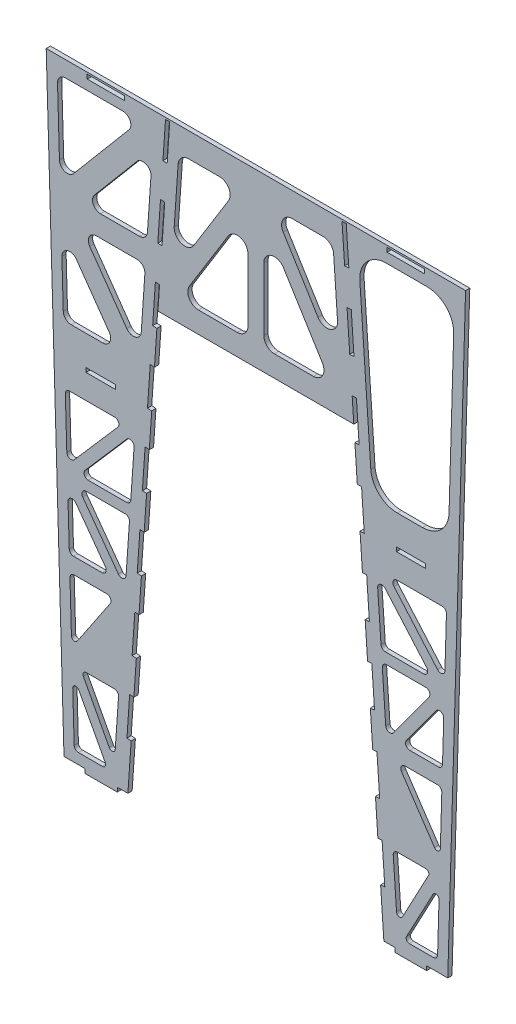
SolidWorks part; units mm, degrees
ref_plane "Front Plane" through (0, 0, 0) normal (0, 0, 1) x (1, 0, 0)
ref_plane "Top Plane" through (0, 0, 0) normal (0, 1, 0) x (1, 0, 0)
ref_plane "Right Plane" through (0, 0, 0) normal (1, 0, 0) x (0, 0, -1)
sketch "Sketch1" plane through (0, 0, 0) normal (0, 0, 1) x (1, 0, 0)
  line L0 (-288.2759, 0) -> (288.2759, 0) construction
  line L1 (-215.8925, 1465.1633) -> (215.8925, 1465.1633)
  line L2 (0, 0) -> (0, 1733.4513) construction
  line L3 (19.05, 1104.9) -> (205.6376, 1104.9)
  line L4 (202.8026, 1145.716) -> (41.4459, 1406.7433)
  line L5 (205.6376, 1104.9) -> (19.05, 1406.7433) construction
  line L6 (205.6376, 1104.9) -> (184.6725, 1406.7433)
  line L7 (183.2417, 1104.9) -> (15.2162, 1376.7154)
  line L8 (19.05, 1406.7433) -> (19.05, 1104.9)
  line L9 (184.6725, 1406.7433) -> (19.05, 1406.7433)
  line L10 (306.6278, 17.4764) -> (234.6272, 1054.1)
  line L12 (459.7218, 17.4764) -> (502.3797, 1465.1633)
  line L13 (459.4357, 7.4824) -> (519.9157, 2060.3987) construction
  line L15 (266.6925, 1465.1633) -> (368.5375, 1465.1633)
  line L16 (-237.2124, 1016.8799) -> (-230.6925, 1110.7494) construction
  line L18 (237.2124, 1016.8799) -> (230.6925, 1110.7494) construction
  line L19 (-408.9218, 7.3164) -> (-332.1008, 7.3164)
  line L20 (-502.3797, 1465.1633) -> (-215.8925, 1465.1633)
  line L22 (408.9218, 7.3164) -> (332.7218, 7.3164)
  line L24 (-408.9218, 17.4764) -> (-408.9218, 7.3164) construction
  line L30 (-408.9218, 17.4764) -> (-408.9218, 7.3164)
  line L31 (502.3797, 1465.1633) -> (368.5375, 1465.1633)
  line L32 (-332.1008, 17.4764) -> (-332.1008, 7.3164) construction
  line L33 (-332.1008, 17.4764) -> (-332.1008, 7.3164)
  line L34 (408.9218, 17.4764) -> (408.9218, 7.3164) construction
  line L35 (408.9218, 17.4764) -> (408.9218, 7.3164)
  line L40 (332.7218, 17.4764) -> (332.7218, 7.3164) construction
  line L43 (332.7218, 17.4764) -> (332.7218, 7.3164)
  line L44 (459.7218, 17.4764) -> (408.9218, 17.4764) construction
  line L45 (459.7218, 17.4764) -> (408.9218, 17.4764)
  line L49 (-408.9218, 17.4764) -> (-459.7218, 17.4764)
  line L52 (-332.1008, 17.4764) -> (-306.6278, 17.4764)
  line L53 (332.7218, 17.4764) -> (306.6278, 17.4764)
  line L55 (-459.7218, 17.4764) -> (-502.3797, 1465.1633)
  line L56 (-459.4357, 7.4824) -> (-519.9157, 2060.3987) construction
  line L81 (215.8925, 1465.1633) -> (266.6925, 1465.1633)
  line L90 (234.6272, 1054.1) -> (-234.6272, 1054.1)
  line L100 (-234.6272, 1054.1) -> (-306.6278, 17.4764)
  line L124 (-184.6725, 1406.7433) -> (-19.05, 1406.7433)
  line L125 (-19.05, 1406.7433) -> (-19.05, 1104.9)
  line L126 (-183.2417, 1104.9) -> (-15.2162, 1376.7154)
  line L127 (-205.6376, 1104.9) -> (-19.05, 1406.7433) construction
  line L128 (-202.8026, 1145.716) -> (-41.4459, 1406.7433)
  line L129 (-205.6376, 1104.9) -> (-184.6725, 1406.7433)
  line L130 (-19.05, 1104.9) -> (-205.6376, 1104.9)
  point P0 (0, 0)
  point P3 (0, 0)
  point P106 (0, 0)
  point P118 (0, 1054.1)
  dimension "D6" = 25.4
  dimension "D7" = 50.8
  dimension "D8" = 58.42
  dimension "D9" = 19.05
  dimension "D19" = 288.2759
  dimension "D22" = 19.05
  dimension "D23" = 19.05
  dimension "D24" = 1054.1
  dimension "D49" = 50.8
extrude "Boss-Extrude1" add sketch "Sketch1" along normal blind 10.16 contours L20 | L100 L90 L125 L130 L129 L124 | L100 | L130 L126 L125 L124 L128 L129 | L81 | L4 L9 L8 L7 L3 L6 | L15 region at (0, 1447.4578, 0) region at (111.9691, 1256.3298, 0) region at (-111.9691, 1256.3298, 0)
fillet "Fillet1" [suppressed] radius 19.05
sketch "Sketch2" plane through (0, 0, 0) normal (0, 0, 1) x (1, 0, 0)
  line L18 (-222.6942, 1372.2749) -> (-212.5765, 1371.5721) construction
  line L56 (-216.5353, 1460.9479) -> (-222.6942, 1372.2749) construction
  line L57 (-212.5765, 1371.5721) -> (-206.3688, 1460.9479) construction
  line L58 (-206.3688, 1460.9479) -> (-216.5353, 1460.9479) construction
  line L59 (-222.6942, 1372.2749) -> (-212.5765, 1371.5721)
  line L61 (-216.5353, 1460.9479) -> (-222.6942, 1372.2749)
  line L63 (-212.5765, 1371.5721) -> (-206.3688, 1460.9479)
  line L176 (-206.3688, 1460.9479) -> (-216.5353, 1460.9479)
  line L181 (-224.8945, 1194.226) -> (-235.0121, 1194.9287) construction
  line L194 (-224.8945, 1194.226) -> (-218.3727, 1288.1221) construction
  line L199 (-218.3727, 1288.1221) -> (-228.4904, 1288.8248) construction
  line L208 (-228.4904, 1288.8248) -> (-235.0121, 1194.9287) construction
  line L213 (-224.8945, 1194.226) -> (-235.0121, 1194.9287)
  line L330 (-224.8945, 1194.226) -> (-218.3727, 1288.1221)
  line L331 (-218.3727, 1288.1221) -> (-228.4904, 1288.8248)
  line L332 (-228.4904, 1288.8248) -> (-235.0121, 1194.9287)
  line L333 (224.8945, 1194.226) -> (235.0121, 1194.9287) construction
  line L334 (235.0121, 1194.9287) -> (228.4904, 1288.8248) construction
  line L335 (218.3727, 1288.1221) -> (224.8945, 1194.226) construction
  line L336 (228.4904, 1288.8248) -> (218.3727, 1288.1221) construction
  line L337 (212.5765, 1371.5721) -> (222.6942, 1372.2749) construction
  line L338 (206.3688, 1460.9479) -> (212.5765, 1371.5721) construction
  line L339 (216.5353, 1460.9479) -> (206.3688, 1460.9479) construction
  line L340 (222.6942, 1372.2749) -> (216.5353, 1460.9479) construction
  line L341 (224.8945, 1194.226) -> (235.0121, 1194.9287)
  line L342 (235.0121, 1194.9287) -> (228.4904, 1288.8248)
  line L343 (218.3727, 1288.1221) -> (224.8945, 1194.226)
  line L344 (228.4904, 1288.8248) -> (218.3727, 1288.1221)
  line L345 (212.5765, 1371.5721) -> (222.6942, 1372.2749)
  line L346 (206.3688, 1460.9479) -> (212.5765, 1371.5721)
  line L347 (216.5353, 1460.9479) -> (206.3688, 1460.9479)
  line L348 (222.6942, 1372.2749) -> (216.5353, 1460.9479)
  line L349 (-240.8102, 1111.4521) -> (-247.33, 1017.5826) construction
  line L350 (-247.33, 1017.5826) -> (-237.2124, 1016.8799) construction
  line L351 (-230.6925, 1110.7494) -> (-240.8102, 1111.4521) construction
  line L353 (-240.8102, 1111.4521) -> (-247.33, 1017.5826)
  line L354 (-247.33, 1017.5826) -> (-237.2124, 1016.8799)
  line L355 (-230.6925, 1110.7494) -> (-240.8102, 1111.4521)
  line L357 (237.2124, 1016.8799) -> (247.33, 1017.5826) construction
  line L358 (247.33, 1017.5826) -> (240.8102, 1111.4521) construction
  line L360 (240.8102, 1111.4521) -> (230.6925, 1110.7494) construction
  line L361 (237.2124, 1016.8799) -> (247.33, 1017.5826)
  line L362 (247.33, 1017.5826) -> (240.8102, 1111.4521)
  line L364 (240.8102, 1111.4521) -> (230.6925, 1110.7494)
  line L365 (-306.6278, 17.4764) -> (-234.6272, 1054.1)
  line L366 (-234.6272, 1054.1) -> (234.6272, 1054.1)
  line L367 (234.6272, 1054.1) -> (306.6278, 17.4764)
  line L372 (408.9218, 17.4764) -> (459.7218, 17.4764)
  line L373 (459.7218, 17.4764) -> (502.3797, 1465.1633)
  line L374 (502.3797, 1465.1633) -> (-502.3797, 1465.1633)
  line L375 (-502.3797, 1465.1633) -> (-459.7218, 17.4764)
  line L376 (-459.7218, 17.4764) -> (-408.9218, 17.4764)
  line L377 (-408.9218, 17.4764) -> (-408.9218, 7.3164)
  line L378 (-408.9218, 7.3164) -> (-332.1008, 7.3164)
  line L379 (-332.1008, 7.3164) -> (-332.1008, 17.4764)
  line L380 (-332.1008, 17.4764) -> (-306.6278, 17.4764)
  line L381 (-298.8019, 130.1492) -> (-292.2913, 223.886)
  line L405 (-243.0122, 933.3767) -> (-253.1299, 934.0795) construction
  line L406 (-253.1299, 934.0795) -> (-259.648, 840.2365) construction
  line L407 (-249.5303, 839.5337) -> (-259.648, 840.2365) construction
  line L408 (-243.0122, 933.3767) -> (-253.1299, 934.0795)
  line L417 (-253.1299, 934.0795) -> (-259.648, 840.2365)
  line L418 (-249.5303, 839.5337) -> (-259.648, 840.2365)
  line L419 (243.0122, 933.3767) -> (253.1299, 934.0795) construction
  line L420 (253.1299, 934.0795) -> (259.648, 840.2365) construction
  line L421 (249.5303, 839.5337) -> (259.648, 840.2365) construction
  line L422 (243.0122, 933.3767) -> (253.1299, 934.0795)
  line L423 (253.1299, 934.0795) -> (259.648, 840.2365)
  line L424 (249.5303, 839.5337) -> (259.648, 840.2365)
  line L425 (-267.6517, 578.6314) -> (-277.7694, 579.3341) construction
  line L426 (-255.332, 756.0041) -> (-265.4497, 756.7068) construction
  line L427 (-265.4497, 756.7068) -> (-271.9659, 662.8903) construction
  line L428 (-261.8482, 662.1876) -> (-271.9659, 662.8903) construction
  line L429 (-277.7694, 579.3341) -> (-284.2838, 485.5442) construction
  line L430 (-274.1661, 484.8415) -> (-284.2838, 485.5442) construction
  line L431 (-274.1661, 484.8415) -> (-284.2838, 485.5442)
  line L432 (-277.7694, 579.3341) -> (-284.2838, 485.5442)
  line L433 (-267.6517, 578.6314) -> (-277.7694, 579.3341)
  line L434 (-261.8482, 662.1876) -> (-271.9659, 662.8903)
  line L435 (-265.4497, 756.7068) -> (-271.9659, 662.8903)
  line L436 (-255.332, 756.0041) -> (-265.4497, 756.7068)
  line L437 (261.8482, 662.1876) -> (271.9659, 662.8903) construction
  line L438 (255.332, 756.0041) -> (265.4497, 756.7068) construction
  line L439 (265.4497, 756.7068) -> (271.9659, 662.8903) construction
  line L440 (261.8482, 662.1876) -> (271.9659, 662.8903)
  line L449 (255.332, 756.0041) -> (265.4497, 756.7068)
  line L450 (265.4497, 756.7068) -> (271.9659, 662.8903)
  line L451 (274.1661, 484.8415) -> (284.2838, 485.5442) construction
  line L452 (277.7694, 579.3341) -> (284.2838, 485.5442) construction
  line L453 (267.6517, 578.6314) -> (277.7694, 579.3341) construction
  line L454 (274.1661, 484.8415) -> (284.2838, 485.5442)
  line L455 (277.7694, 579.3341) -> (284.2838, 485.5442)
  line L456 (267.6517, 578.6314) -> (277.7694, 579.3341)
  line L457 (-298.8019, 130.1492) -> (-308.9196, 130.8519) construction
  line L458 (-302.4089, 224.5888) -> (-308.9196, 130.8519) construction
  line L459 (-292.2913, 223.886) -> (-302.4089, 224.5888) construction
  line L460 (-286.484, 307.4953) -> (-296.6017, 308.1981) construction
  line L461 (-290.0892, 401.9615) -> (-296.6017, 308.1981) construction
  line L462 (-279.9715, 401.2587) -> (-290.0892, 401.9615) construction
  line L463 (-298.8019, 130.1492) -> (-308.9196, 130.8519)
  line L464 (-302.4089, 224.5888) -> (-308.9196, 130.8519)
  line L465 (-292.2913, 223.886) -> (-302.4089, 224.5888)
  line L466 (-286.484, 307.4953) -> (-296.6017, 308.1981)
  line L467 (-290.0892, 401.9615) -> (-296.6017, 308.1981)
  line L468 (-279.9715, 401.2587) -> (-290.0892, 401.9615)
  line L469 (286.484, 307.4953) -> (296.6017, 308.1981) construction
  line L470 (279.9715, 401.2587) -> (290.0892, 401.9615) construction
  line L471 (290.0892, 401.9615) -> (296.6017, 308.1981) construction
  line L472 (286.484, 307.4953) -> (296.6017, 308.1981)
  line L473 (279.9715, 401.2587) -> (290.0892, 401.9615)
  line L474 (290.0892, 401.9615) -> (296.6017, 308.1981)
  line L475 (298.8019, 130.1492) -> (308.9196, 130.8519) construction
  line L476 (302.4089, 224.5888) -> (308.9196, 130.8519) construction
  line L477 (292.2913, 223.886) -> (302.4089, 224.5888) construction
  line L478 (298.8019, 130.1492) -> (308.9196, 130.8519)
  line L479 (302.4089, 224.5888) -> (308.9196, 130.8519)
  line L480 (292.2913, 223.886) -> (302.4089, 224.5888)
  line L481 (-230.6925, 1110.7494) -> (-237.2124, 1016.8799)
  line L482 (243.0122, 933.3767) -> (249.5303, 839.5337)
  line L483 (255.332, 756.0041) -> (261.8482, 662.1876)
  line L484 (-249.5303, 839.5337) -> (-243.0122, 933.3767)
  line L485 (-261.8482, 662.1876) -> (-255.332, 756.0041)
  line L486 (267.6517, 578.6314) -> (274.1661, 484.8415)
  line L487 (-286.484, 307.4953) -> (-279.9715, 401.2587)
  line L488 (-274.1661, 484.8415) -> (-267.6517, 578.6314)
  line L489 (279.9715, 401.2587) -> (286.484, 307.4953)
  line L490 (292.2913, 223.886) -> (298.8019, 130.1492)
  line L492 (230.6925, 1110.7494) -> (237.2124, 1016.8799)
  line L499 (306.6278, 17.4764) -> (332.7218, 17.4764)
  line L500 (332.7218, 17.4764) -> (332.7218, 7.3164)
  line L501 (332.7218, 7.3164) -> (408.9218, 7.3164)
  line L502 (408.9218, 7.3164) -> (408.9218, 17.4764)
  dimension "D1" = 0
extrude "Cut-Extrude5" cut sketch "Sketch2" along normal blind 12.7
sketch "Sketch4" plane through (0, 0, 10.16) normal (0, 0, 1) x (1, 0, 0)
  line L0 (404.2136, 1450.7879) -> (404.2136, 1460.9479) construction
  line L1 (314.2136, 1450.7879) -> (404.2136, 1450.7879) construction
  line L2 (314.2136, 1450.7879) -> (314.2136, 1460.9479) construction
  line L3 (404.2136, 1460.9479) -> (314.2136, 1460.9479) construction
  line L4 (404.2136, 1450.7879) -> (404.2136, 1460.9479)
  line L5 (314.2136, 1450.7879) -> (404.2136, 1450.7879)
  line L6 (314.2136, 1450.7879) -> (314.2136, 1460.9479)
  line L7 (404.2136, 1460.9479) -> (314.2136, 1460.9479)
  line L8 (336.7821, 840.6279) -> (336.7821, 850.7879) construction
  line L9 (336.7821, 840.6279) -> (406.7821, 840.6279) construction
  line L10 (406.7821, 840.6279) -> (406.7821, 850.7879) construction
  line L11 (406.7821, 850.7879) -> (336.7821, 850.7879) construction
  line L12 (336.7821, 840.6279) -> (336.7821, 850.7879)
  line L13 (336.7821, 840.6279) -> (406.7821, 840.6279)
  line L14 (406.7821, 840.6279) -> (406.7821, 850.7879)
  line L15 (406.7821, 850.7879) -> (336.7821, 850.7879)
extrude "Cut-Extrude6" cut sketch "Sketch4" against normal through all both
ref_plane "Plane1" through (0, 0, 0) normal (1, 0, 0) x (0, 0, -1)
mirror "Mirror1" about plane through (0, 0, 0) normal (1, 0, 0) of "Cut-Extrude6"
sketch "Sketch5" plane through (0, 0, 10.16) normal (0, 0, 1) x (1, 0, 0)
  line L0 (435.0592, 42.8764) -> (475.846, 1427.0633)
  line L1 (475.846, 1427.0633) -> (244.35, 1427.0633)
  line L2 (244.35, 1427.0633) -> (340.4913, 42.8764)
  line L3 (340.4913, 42.8764) -> (435.0592, 42.8764)
  line L4 (281.2007, 896.5079) -> (460.2126, 896.5079)
  line L5 (457.2188, 794.9079) -> (288.2575, 794.9079)
  line L6 (336.7821, 840.6279) -> (406.7821, 840.6279) construction
  line L7 (475.846, 1427.0633) -> (460.2126, 896.5079)
  line L8 (468.0293, 1161.7856) -> (281.2007, 896.5079) construction
  line L9 (244.35, 1427.0633) -> (468.0293, 1161.7856) construction
  line L10 (244.35, 1427.0633) -> (281.2007, 896.5079)
  line L11 (281.2007, 896.5079) -> (244.35, 1427.0633)
  line L12 (262.7753, 1161.7856) -> (468.0293, 1161.7856) construction
  line L13 (435.0592, 42.8764) -> (457.2188, 794.9079)
  line L14 (446.139, 418.8922) -> (457.2188, 794.9079)
  line L15 (451.6789, 606.9001) -> (288.2575, 794.9079) construction
  line L16 (451.6789, 606.9001) -> (314.3744, 418.8922) construction
  line L17 (446.139, 418.8922) -> (435.0592, 42.8764)
  line L18 (440.5991, 230.8843) -> (314.3744, 418.8922) construction
  line L19 (440.5991, 230.8843) -> (340.4913, 42.8764) construction
  line L20 (451.6789, 606.9001) -> (301.316, 606.9001) construction
  line L21 (314.3744, 418.8922) -> (446.139, 418.8922) construction
  line L22 (440.5991, 230.8843) -> (327.4329, 230.8843) construction
  line L23 (354.8795, 42.8764) -> (439.7562, 202.2796)
  line L24 (338.831, 66.78) -> (419.4486, 218.1843)
  line L25 (328.315, 218.1843) -> (419.4486, 218.1843)
  line L26 (326.5508, 243.5843) -> (416.7758, 243.5843)
  line L27 (416.7758, 243.5843) -> (316.1395, 393.479)
  line L28 (441.2422, 252.7104) -> (338.1977, 406.1922)
  line L29 (338.1977, 406.1922) -> (445.7648, 406.1922)
  line L30 (446.8874, 444.2922) -> (348.6506, 444.2922)
  line L31 (348.6506, 444.2922) -> (451.0177, 584.4611)
  line L32 (313.0087, 438.5556) -> (426.6777, 594.2001)
  line L33 (426.6777, 594.2001) -> (302.1981, 594.2001)
  line L34 (300.4339, 619.6001) -> (423.8126, 619.6001)
  line L35 (423.8126, 619.6001) -> (289.7189, 773.8679)
  line L36 (452.2306, 625.6241) -> (316.1239, 782.2079)
  line L37 (316.1239, 782.2079) -> (456.8446, 782.2079)
  line L38 (277.5742, 1427.0633) -> (469.1512, 1199.8582)
  line L39 (247.3325, 1384.1232) -> (413.3881, 1187.1856)
  line L40 (413.3881, 1187.1856) -> (261.0111, 1187.1856)
  line L41 (264.5396, 1136.3856) -> (419.0736, 1136.3856)
  line L42 (419.0736, 1136.3856) -> (278.4119, 936.6601)
  line L43 (466.6727, 1115.7474) -> (330.1564, 921.9079)
  line L44 (330.1564, 921.9079) -> (460.961, 921.9079)
  line L64 (-234.6272, 1054.1) -> (234.6272, 1054.1)
  line L65 (234.6272, 1054.1) -> (230.6925, 1110.7494)
  line L66 (230.6925, 1110.7494) -> (240.8102, 1111.4521)
  line L67 (240.8102, 1111.4521) -> (247.33, 1017.5826)
  line L68 (247.33, 1017.5826) -> (237.2124, 1016.8799)
  line L69 (237.2124, 1016.8799) -> (243.0122, 933.3767)
  line L70 (243.0122, 933.3767) -> (253.1299, 934.0795)
  line L71 (253.1299, 934.0795) -> (259.648, 840.2365)
  line L72 (259.648, 840.2365) -> (249.5303, 839.5337)
  line L73 (249.5303, 839.5337) -> (255.332, 756.0041)
  line L74 (255.332, 756.0041) -> (265.4497, 756.7068)
  line L75 (265.4497, 756.7068) -> (271.9659, 662.8903)
  line L76 (271.9659, 662.8903) -> (261.8482, 662.1876)
  line L77 (261.8482, 662.1876) -> (267.6517, 578.6314)
  line L78 (267.6517, 578.6314) -> (277.7694, 579.3341)
  line L79 (277.7694, 579.3341) -> (284.2838, 485.5442)
  line L80 (284.2838, 485.5442) -> (274.1661, 484.8415)
  line L81 (274.1661, 484.8415) -> (279.9715, 401.2587)
  line L82 (279.9715, 401.2587) -> (290.0892, 401.9615)
  line L83 (290.0892, 401.9615) -> (296.6017, 308.1981)
  line L84 (296.6017, 308.1981) -> (286.484, 307.4953)
  line L85 (286.484, 307.4953) -> (292.2913, 223.886)
  line L86 (292.2913, 223.886) -> (302.4089, 224.5888)
  line L87 (302.4089, 224.5888) -> (308.9196, 130.8519)
  line L88 (308.9196, 130.8519) -> (298.8019, 130.1492)
  line L89 (298.8019, 130.1492) -> (306.6278, 17.4764)
  line L90 (306.6278, 17.4764) -> (332.7218, 17.4764)
  line L91 (332.7218, 17.4764) -> (332.7218, 7.3164)
  line L92 (332.7218, 7.3164) -> (408.9218, 7.3164)
  line L93 (408.9218, 7.3164) -> (408.9218, 17.4764)
  line L94 (408.9218, 17.4764) -> (459.7218, 17.4764)
  line L95 (459.7218, 17.4764) -> (502.3797, 1465.1633)
  line L96 (502.3797, 1465.1633) -> (-502.3797, 1465.1633)
  line L97 (-502.3797, 1465.1633) -> (-459.7218, 17.4764)
  line L98 (-459.7218, 17.4764) -> (-408.9218, 17.4764)
  line L99 (-408.9218, 17.4764) -> (-408.9218, 7.3164)
  line L100 (-408.9218, 7.3164) -> (-332.1008, 7.3164)
  line L101 (-332.1008, 7.3164) -> (-332.1008, 17.4764)
  line L102 (-332.1008, 17.4764) -> (-306.6278, 17.4764)
  line L103 (-306.6278, 17.4764) -> (-298.8019, 130.1492)
  line L104 (-298.8019, 130.1492) -> (-308.9196, 130.8519)
  line L105 (-308.9196, 130.8519) -> (-302.4089, 224.5888)
  line L106 (-302.4089, 224.5888) -> (-292.2913, 223.886)
  line L107 (-292.2913, 223.886) -> (-286.484, 307.4953)
  line L108 (-286.484, 307.4953) -> (-296.6017, 308.1981)
  line L109 (-296.6017, 308.1981) -> (-290.0892, 401.9615)
  line L110 (-290.0892, 401.9615) -> (-279.9715, 401.2587)
  line L111 (-279.9715, 401.2587) -> (-274.1661, 484.8415)
  line L112 (-274.1661, 484.8415) -> (-284.2838, 485.5442)
  line L113 (-284.2838, 485.5442) -> (-277.7694, 579.3341)
  line L114 (-277.7694, 579.3341) -> (-267.6517, 578.6314)
  line L115 (-267.6517, 578.6314) -> (-261.8482, 662.1876)
  line L116 (-261.8482, 662.1876) -> (-271.9659, 662.8903)
  line L117 (-271.9659, 662.8903) -> (-265.4497, 756.7068)
  line L118 (-265.4497, 756.7068) -> (-255.332, 756.0041)
  line L119 (-255.332, 756.0041) -> (-249.5303, 839.5337)
  line L120 (-249.5303, 839.5337) -> (-259.648, 840.2365)
  line L121 (-259.648, 840.2365) -> (-253.1299, 934.0795)
  line L122 (-253.1299, 934.0795) -> (-243.0122, 933.3767)
  line L123 (-243.0122, 933.3767) -> (-237.2124, 1016.8799)
  line L124 (-237.2124, 1016.8799) -> (-247.33, 1017.5826)
  line L125 (-247.33, 1017.5826) -> (-240.8102, 1111.4521)
  line L126 (-240.8102, 1111.4521) -> (-230.6925, 1110.7494)
  line L127 (-230.6925, 1110.7494) -> (-234.6272, 1054.1)
  line L128 (-234.6272, 1054.1) -> (234.6272, 1054.1)
  line L129 (234.6272, 1054.1) -> (230.6925, 1110.7494)
  line L130 (230.6925, 1110.7494) -> (240.8102, 1111.4521)
  line L131 (240.8102, 1111.4521) -> (247.33, 1017.5826)
  line L132 (247.33, 1017.5826) -> (237.2124, 1016.8799)
  line L133 (237.2124, 1016.8799) -> (243.0122, 933.3767)
  line L134 (243.0122, 933.3767) -> (253.1299, 934.0795)
  line L135 (253.1299, 934.0795) -> (259.648, 840.2365)
  line L136 (259.648, 840.2365) -> (249.5303, 839.5337)
  line L137 (249.5303, 839.5337) -> (255.332, 756.0041)
  line L138 (255.332, 756.0041) -> (265.4497, 756.7068)
  line L139 (265.4497, 756.7068) -> (271.9659, 662.8903)
  line L140 (271.9659, 662.8903) -> (261.8482, 662.1876)
  line L141 (261.8482, 662.1876) -> (267.6517, 578.6314)
  line L142 (267.6517, 578.6314) -> (277.7694, 579.3341)
  line L143 (277.7694, 579.3341) -> (284.2838, 485.5442)
  line L144 (284.2838, 485.5442) -> (274.1661, 484.8415)
  line L145 (274.1661, 484.8415) -> (279.9715, 401.2587)
  line L146 (279.9715, 401.2587) -> (290.0892, 401.9615)
  line L147 (290.0892, 401.9615) -> (296.6017, 308.1981)
  line L148 (296.6017, 308.1981) -> (286.484, 307.4953)
  line L149 (286.484, 307.4953) -> (292.2913, 223.886)
  line L150 (292.2913, 223.886) -> (302.4089, 224.5888)
  line L151 (302.4089, 224.5888) -> (308.9196, 130.8519)
  line L152 (308.9196, 130.8519) -> (298.8019, 130.1492)
  line L153 (298.8019, 130.1492) -> (306.6278, 17.4764)
  line L154 (306.6278, 17.4764) -> (332.7218, 17.4764)
  line L155 (332.7218, 17.4764) -> (332.7218, 7.3164)
  line L156 (332.7218, 7.3164) -> (408.9218, 7.3164)
  line L157 (408.9218, 7.3164) -> (408.9218, 17.4764)
  line L158 (408.9218, 17.4764) -> (459.7218, 17.4764)
  line L159 (459.7218, 17.4764) -> (502.3797, 1465.1633)
  line L160 (502.3797, 1465.1633) -> (-502.3797, 1465.1633)
  line L161 (-502.3797, 1465.1633) -> (-459.7218, 17.4764)
  line L162 (-459.7218, 17.4764) -> (-408.9218, 17.4764)
  line L163 (-408.9218, 17.4764) -> (-408.9218, 7.3164)
  line L164 (-408.9218, 7.3164) -> (-332.1008, 7.3164)
  line L165 (-332.1008, 7.3164) -> (-332.1008, 17.4764)
  line L166 (-332.1008, 17.4764) -> (-306.6278, 17.4764)
  line L167 (-306.6278, 17.4764) -> (-298.8019, 130.1492)
  line L168 (-298.8019, 130.1492) -> (-308.9196, 130.8519)
  line L169 (-308.9196, 130.8519) -> (-302.4089, 224.5888)
  line L170 (-302.4089, 224.5888) -> (-292.2913, 223.886)
  line L171 (-292.2913, 223.886) -> (-286.484, 307.4953)
  line L172 (-286.484, 307.4953) -> (-296.6017, 308.1981)
  line L173 (-296.6017, 308.1981) -> (-290.0892, 401.9615)
  line L174 (-290.0892, 401.9615) -> (-279.9715, 401.2587)
  line L175 (-279.9715, 401.2587) -> (-274.1661, 484.8415)
  line L176 (-274.1661, 484.8415) -> (-284.2838, 485.5442)
  line L177 (-284.2838, 485.5442) -> (-277.7694, 579.3341)
  line L178 (-277.7694, 579.3341) -> (-267.6517, 578.6314)
  line L179 (-267.6517, 578.6314) -> (-261.8482, 662.1876)
  line L180 (-261.8482, 662.1876) -> (-271.9659, 662.8903)
  line L181 (-271.9659, 662.8903) -> (-265.4497, 756.7068)
  line L182 (-265.4497, 756.7068) -> (-255.332, 756.0041)
  line L183 (-255.332, 756.0041) -> (-249.5303, 839.5337)
  line L184 (-249.5303, 839.5337) -> (-259.648, 840.2365)
  line L185 (-259.648, 840.2365) -> (-253.1299, 934.0795)
  line L186 (-253.1299, 934.0795) -> (-243.0122, 933.3767)
  line L187 (-243.0122, 933.3767) -> (-237.2124, 1016.8799)
  line L188 (-237.2124, 1016.8799) -> (-247.33, 1017.5826)
  line L189 (-247.33, 1017.5826) -> (-240.8102, 1111.4521)
  line L190 (-240.8102, 1111.4521) -> (-230.6925, 1110.7494)
  line L191 (-230.6925, 1110.7494) -> (-234.6272, 1054.1)
  dimension "D2" = 38.1
  dimension "D3" = 25.4
  dimension "D4" = 25.4
  dimension "D5" = 25.4
  dimension "D6" = 101.6
  dimension "D7" = 45.72
  dimension "D8" = 12.7
  dimension "D9" = 12.7
  dimension "D10" = 12.7
  dimension "D11" = 12.7
  dimension "D12" = 12.7
  dimension "D13" = 12.7
  dimension "D14" = 12.7
  dimension "D15" = 25.4
  dimension "D16" = 12.7
  dimension "D17" = 12.7
  dimension "D18" = 12.7
  dimension "D19" = 12.7
  dimension "D20" = 12.7
  dimension "D21" = 12.7
  dimension "D22" = 12.7
  dimension "D23" = 25.4
  dimension "D24" = 25.4
  dimension "D25" = 25.4
  dimension "D26" = 25.4
  dimension "D27" = 25.4
  dimension "D28" = 25.4
  dimension "D29" = 25.4
  dimension "D1" = 0
extrude "Cut-Extrude7" cut sketch "Sketch5" against normal through all both contours L1 L38 L7 | L40 L39 L11 | L42 L41 L11 | L43 L44 L7 | L37 L36 L14 | L34 L35 L2 | L32 L33 L2 | L31 L30 L14 | L29 L28 L0 | L26 L27 L2 | L25 L2 L24 | L23 L3 L0 region at (409.8983, 96.0108, 10.16) region at (408.4016, 355.0316, 10.16) region at (362.1982, 167.7162, 10.16) region at (415.5186, 491.0151, 10.16) region at (353.1554, 293.5492, 10.16) region at (408.3997, 730.0133, 10.16) region at (347.2948, 542.3186, 10.16) region at (337.9884, 671.0227, 10.16) region at (419.2634, 986.5211, 10.16) region at (320.675, 1069.8105, 10.16) region at (407.5238, 1351.3283, 10.16) region at (307.2439, 1252.8315, 10.16)
fillet "Fillet3" radius 10.16 18 edges at (446.8874, 444.2922, 5.08) (416.7758, 243.5843, 5.08) (338.1977, 406.1922, 5.08) (348.6506, 444.2922, 5.08) (445.7648, 406.1922, 5.08) (326.5508, 243.5843, 5.08) (313.0087, 438.5556, 5.08) (451.0177, 584.4611, 5.08) (426.6777, 594.2001, 5.08) (302.1981, 594.2001, 5.08) (300.4339, 619.6001, 5.08) (423.8126, 619.6001, 5.08) (452.2306, 625.6241, 5.08) (289.7189, 773.8679, 5.08) (316.1239, 782.2079, 5.08) (456.8446, 782.2079, 5.08) (435.0592, 42.8764, 5.08) (328.315, 218.1843, 5.08)
fillet "Fillet4" radius 7.62 6 edges at (354.8795, 42.8764, 5.08) (419.4486, 218.1843, 5.08) (316.1395, 393.479, 5.08) (439.7562, 202.2796, 5.08) (338.831, 66.78, 5.08) (441.2422, 252.7104, 5.08)
fillet "Fillet5" radius 19.05 12 edges at (330.1564, 921.9079, 5.08) (460.961, 921.9079, 5.08) (419.0736, 1136.3856, 5.08) (466.6727, 1115.7474, 5.08) (475.846, 1427.0633, 5.08) (469.1512, 1199.8582, 5.08) (413.3881, 1187.1856, 5.08) (277.5742, 1427.0633, 5.08) (247.3325, 1384.1232, 5.08) (264.5396, 1136.3856, 5.08) (261.0111, 1187.1856, 5.08) (278.4119, 936.6601, 5.08)
mirror "Mirror2" about plane through (0, 0, 0) normal (1, 0, 0) of "Cut-Extrude7", "Fillet3", "Fillet4", "Fillet5"
sketch "Sketch6" plane through (0, 0, 10.16) normal (0, 0, 1) x (1, 0, 0)
  line L0 (244.35, 1427.0633) -> (279.4365, 921.9079)
  line L1 (279.4365, 921.9079) -> (460.961, 921.9079)
  line L2 (460.961, 921.9079) -> (475.846, 1427.0633)
  line L3 (366.8731, 921.9079) -> (442.4641, 921.9079) construction
  line L4 (244.35, 1427.0633) -> (475.846, 1427.0633)
  line L5 (470.6195, 1249.6909) -> (475.2682, 1407.4522) construction
  line L6 (251.3752, 1325.9178) -> (259.7797, 1204.9157) construction
  line L7 (456.2264, 1427.0633) -> (318.5551, 1427.0633) construction
extrude "Cut-Extrude8" cut sketch "Sketch6" against normal through all both
fillet "Fillet6" radius 63.5 4 edges at (475.846, 1427.0633, 5.08) (460.961, 921.9079, 5.08) (279.4365, 921.9079, 5.08) (244.35, 1427.0633, 5.08)
sketch "Sketch7" plane through (0, 0, 10.16) normal (0, 0, 1) x (1, 0, 0)
  line L0 (-336.0296, 243.5843) -> (-397.7172, 243.5843) construction
  line L1 (-318.1167, 365.0131) -> (-325.894, 253.0403) construction
  line L2 (-406.1524, 259.4075) -> (-332.0448, 369.7885) construction
  line L3 (-336.0296, 243.5843) -> (-397.7172, 243.5843)
  line L4 (-318.1167, 365.0131) -> (-325.894, 253.0403)
  line L5 (-406.1524, 259.4075) -> (-332.0448, 369.7885)
  arc A0 (-406.1524, 259.4075) -> (-397.7172, 243.5843) centre (-397.7172, 253.7443) ccw construction
  arc A1 (-336.0296, 243.5843) -> (-325.894, 253.0403) centre (-336.0296, 253.7443) ccw construction
  arc A2 (-318.1167, 365.0131) -> (-332.0448, 369.7885) centre (-325.7184, 365.5411) ccw construction
  arc A3 (-406.1524, 259.4075) -> (-397.7172, 243.5843) centre (-397.7172, 253.7443) ccw
  arc A4 (-336.0296, 243.5843) -> (-325.894, 253.0403) centre (-336.0296, 253.7443) ccw
  arc A5 (-318.1167, 365.0131) -> (-332.0448, 369.7885) centre (-325.7184, 365.5411) ccw
extrude "Boss-Extrude2" add sketch "Sketch7" against normal up to surface (10.16 mm away) contours A3 L3 A4 L4 A5 L5 up to face at (-346.4743, 545.9059, 0)
mirror "Mirror3" about plane through (0, 0, 0) normal (1, 0, 0) of "Boss-Extrude2"
fillet "Fillet7" radius 25.4 12 edges at (183.2417, 1104.9, 5.08) (-19.05, 1104.9, 5.08) (202.8026, 1145.716, 5.08) (19.05, 1104.9, 5.08) (-202.8026, 1145.716, 5.08) (-183.2417, 1104.9, 5.08) (-184.6725, 1406.7433, 5.08) (41.4459, 1406.7433, 5.08) (19.05, 1370.5134, 5.08) (-19.05, 1370.5134, 5.08) (-41.4459, 1406.7433, 5.08) (184.6725, 1406.7433, 5.08)
